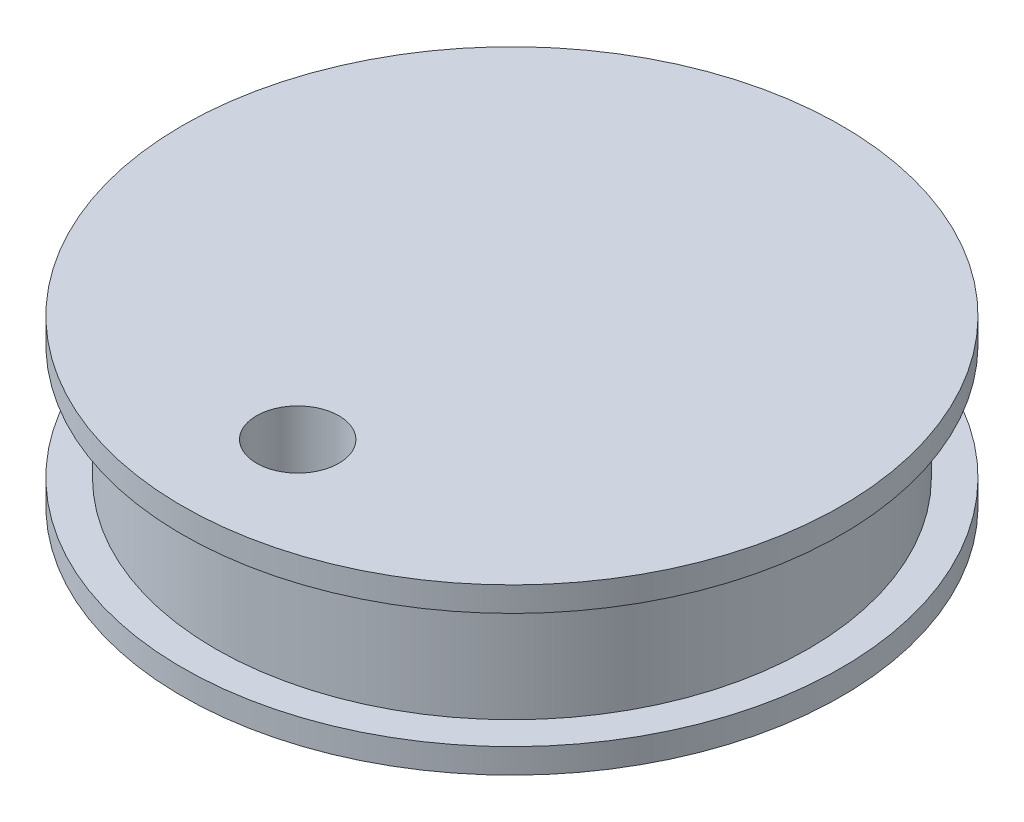
SolidWorks part; units mm, degrees
ref_plane "Front Plane" through (0, 0, 0) normal (0, 0, 1) x (1, 0, 0)
ref_plane "Top Plane" through (0, 0, 0) normal (0, 1, 0) x (1, 0, 0)
ref_plane "Right Plane" through (0, 0, 0) normal (1, 0, 0) x (0, 0, -1)
sketch "Sketch3" plane through (0, 0, 0) normal (0, 0, 1) x (1, 0, 0)
  line L0 (25.4, -1.3614) -> (50.8, -1.3614)
  line L1 (50.8, -1.3614) -> (50.8, 0.5436)
  line L2 (50.8, 0.5436) -> (48.26, 0.5436)
  line L3 (48.26, 0.5436) -> (48.26, 9.4336)
  line L4 (48.26, 9.4336) -> (50.8, 9.4336)
  line L5 (50.8, 9.4336) -> (50.8, 11.3386)
  line L6 (50.8, 11.3386) -> (25.4, 11.3386)
  line L7 (25.4, 11.3386) -> (25.4, -1.3614)
  dimension "D1" = 25.4
  dimension "D2" = 25.4
  dimension "D3" = 8.89
  dimension "D4" = 12.7
  dimension "D5" = 2.54
  dimension "D6" = 1.905
revolve "Revolve1" add sketch "Sketch3" angle 360 about L7
sketch "Sketch4" plane through (0, 11.3386, 0) normal (0, 1, 0) x (1, 0, 0)
  line L0 (25.4, -1.3284) -> (25.4, -25.4) construction
  line L1 (25.4, -25.4) -> (25.4, 25.4) construction
  line L2 (25.4, 25.4) -> (25.4, 0) construction
  line L3 (25.4, 0) -> (50.8, 0) construction
  line L4 (50.8, 0) -> (0, 0) construction
  circle A0 centre (25.4, -16.51) radius 3.175
  circle A1 centre (25.4, 0) radius 25.4 construction
  point P13 (0, 0.5027)
  dimension "D3" = 6.35
  dimension "D1" = 0
  dimension "D2" = 16.51
extrude "Cut-Extrude1" cut sketch "Sketch4" against normal through all
